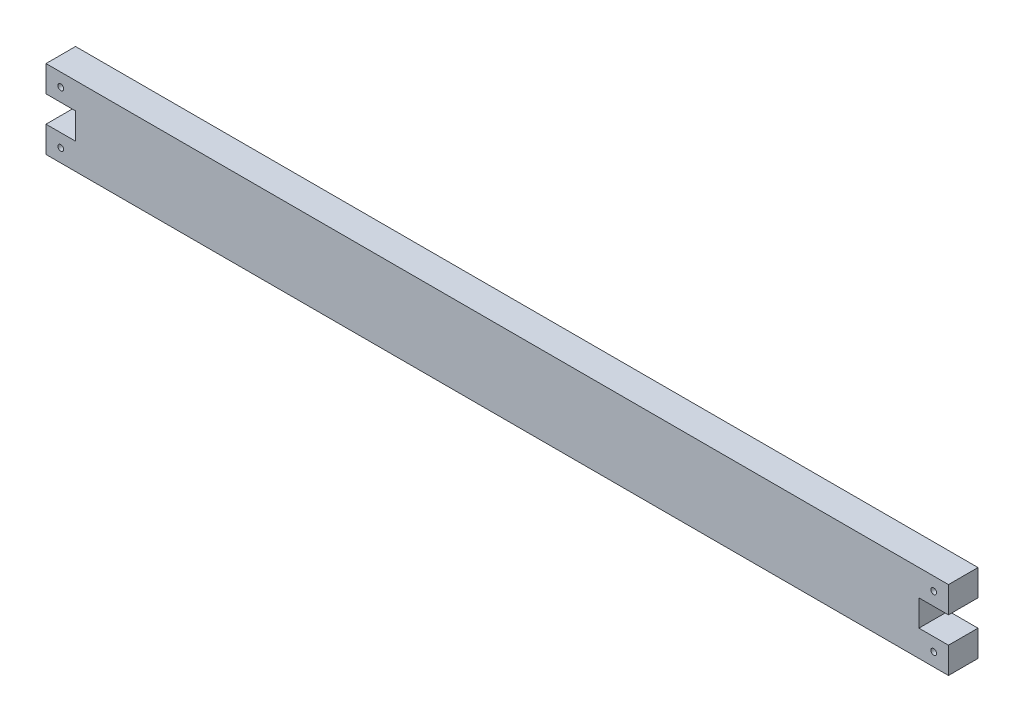
SolidWorks part; units mm, degrees
material "Teak"
ref_plane "Front Plane" through (0, 0, 0) normal (0, 0, 1) x (1, 0, 0)
ref_plane "Top Plane" through (0, 0, 0) normal (0, 1, 0) x (1, 0, 0)
ref_plane "Right Plane" through (0, 0, 0) normal (1, 0, 0) x (0, 0, -1)
sketch "Sketch1" plane through (0, 0, 0) normal (0, 0, 1) x (1, 0, 0)
  line L1 (-275, 24) -> (275, 24)
  line L2 (-275, 24) -> (-275, -24)
  line L3 (-275, -24) -> (275, -24)
  line L4 (275, 24) -> (275, -24)
  line L5 (-275, 24) -> (275, -24) construction
  line L6 (-275, -24) -> (275, 24) construction
  point P0 (0, 0)
  dimension "D1" = 550
  dimension "D2" = 48
extrude "Основа" add sketch "Sketch1" along normal blind 18
sketch "Sketch2" plane through (0, 0, 18) normal (0, 0, 1) x (1, 0, 0)
  line L0 (-275, -8) -> (-257, -8)
  line L1 (-275, 24) -> (-275, -24) construction
  line L2 (-257, -8) -> (-257, 8)
  line L3 (-257, 8) -> (-275, 8)
  line L4 (-275, 8) -> (-275, -8)
  line L5 (0, 24) -> (0, -24) construction
  line L6 (275, 24) -> (-275, 24) construction
  line L7 (-275, -24) -> (275, -24) construction
  point P13 (-275, 0)
  point P14 (-275, 0)
  dimension "D1" = 18
  dimension "D2" = 16
extrude "Шип" cut sketch "Sketch2" against normal up to next
sketch "Sketch3" plane through (0, 0, 18) normal (0, 0, 1) x (1, 0, 0)
  line L0 (-257, 8) -> (-275, 8) construction
  line L1 (-275, 24) -> (-275, 8) construction
  line L2 (-275, -8) -> (-275, -24) construction
  circle A0 centre (-266, 16) radius 1.75
  circle A1 centre (-266, -16) radius 1.75
  point P7 (-266, 8)
  point P12 (-275, 16)
  point P16 (-275, -16)
  dimension "D1" = 3.5
extrude "Крепежные" cut sketch "Sketch3" against normal up to next
mirror "Mirror1" about plane through (0, 0, 0) normal (1, 0, 0) of "Крепежные", "Шип"
